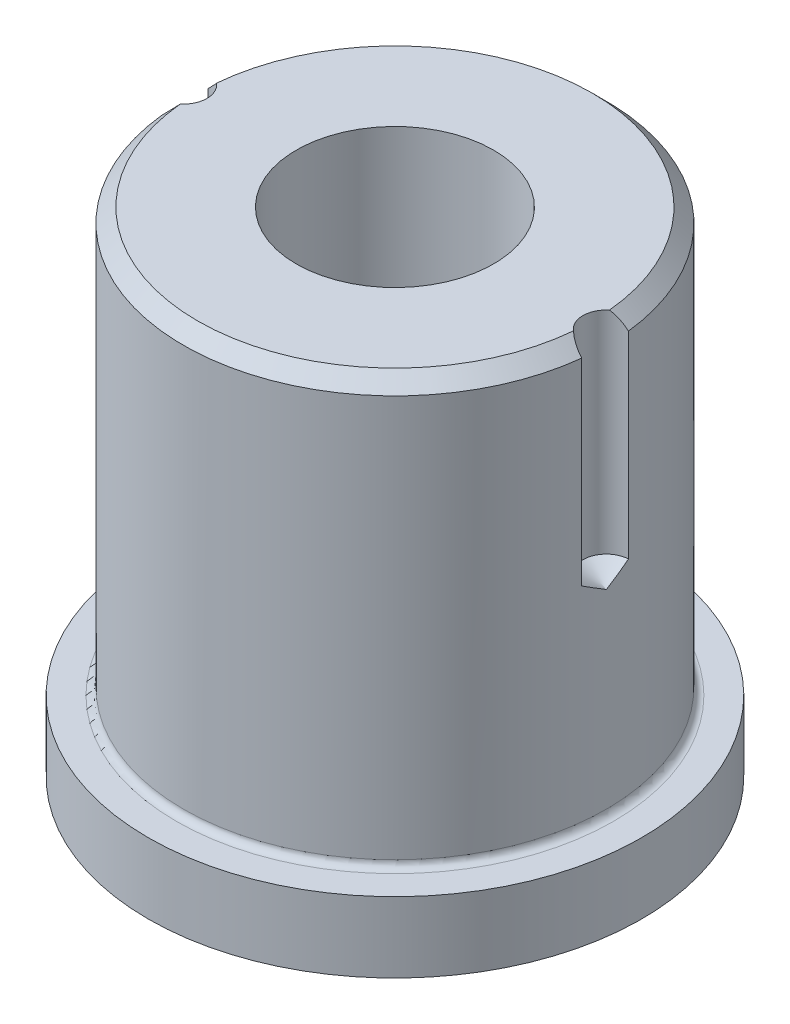
SolidWorks part; units mm, degrees
material "Commercial Bronze, UNS C22000 (90-10 Bronze)"
ref_plane "Front Plane" through (0, 0, 0) normal (0, 0, 1) x (1, 0, 0)
ref_plane "Top Plane" through (0, 0, 0) normal (0, 1, 0) x (1, 0, 0)
ref_plane "Right Plane" through (0, 0, 0) normal (1, 0, 0) x (0, 0, -1)
sketch "Sketch1" plane through (0, 0, 0) normal (0, 1, 0) x (1, 0, 0)
  circle A0 centre (0, 0) radius 35
  dimension "D1" = 70
extrude "Boss-Extrude1" add sketch "Sketch1" along normal blind 10
sketch "Sketch2" plane through (0, 10, 0) normal (0, 1, 0) x (1, 0, 0)
  circle A0 centre (0, 0) radius 30
  dimension "D1" = 60
extrude "Boss-Extrude2" add sketch "Sketch2" along normal blind 60
sketch "Sketch3" plane through (0, 70, 0) normal (0, 1, 0) x (1, 0, 0)
  circle A0 centre (0, 0) radius 14
  dimension "D1" = 28
extrude "Cut-Extrude1" cut sketch "Sketch3" against normal through all
chamfer "Chamfer1" distance 2 angle 45 1 edges at (0, 70, 30)
hole_wizard "Ø8.0mm Dowel Hole1" positions "Sketch4" profile "Sketch5" hole size "Ø8.0" standard "ISO"
sketch "Sketch4" plane through (0, 70, 0) normal (0, 1, 0) x (1, 0, 0)
  circle A0 centre (0, 0) radius 30 construction
  circle A1 centre (0, 0) radius 30 construction
  point P0 (-30, 0)
  point P4 (30, 0)
sketch "Sketch5" plane through (-30, 70, 0) normal (1, 0, 0) x (0, 0, 1)
  line L0 (0, 0) -> (0, 31.997)
  line L1 (0, 31.997) -> (3.3235, 30)
  line L2 (3.3235, 30) -> (3.3235, 0)
  line L5 (3.3235, 0) -> (0, 0)
  line L10 (0, 31.997) -> (-3.3235, 30) construction
  line L11 (0, -6.35) -> (0, 107.95) construction
  dimension "Hole Dia." = 6.647
  dimension "Hole Depth" = 30
  dimension "Drill Angle" = 118
fillet "Fillet1" radius 1 1 edges at (0, 10, 30)
